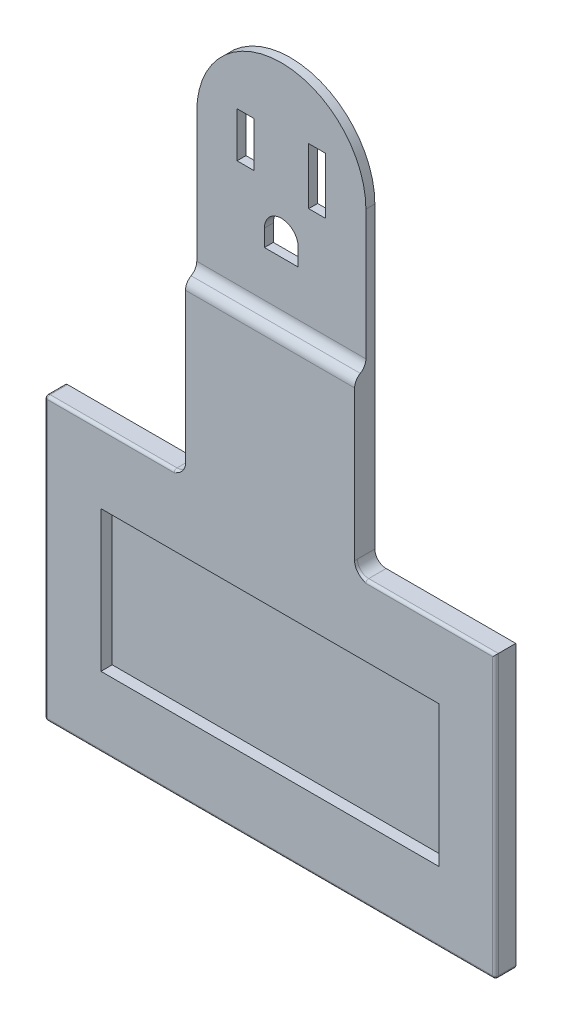
SolidWorks part; units mm, degrees
ref_plane "Front Plane" through (0, 0, 0) normal (0, 0, 1) x (1, 0, 0)
ref_plane "Top Plane" through (0, 0, 0) normal (0, 1, 0) x (1, 0, 0)
ref_plane "Right Plane" through (0, 0, 0) normal (1, 0, 0) x (0, 0, -1)
sketch "Sketch1" plane through (0, 0, 0) normal (0, 0, 1) x (1, 0, 0)
  line L0 (8.022, -0.6939) -> (8.022, -8.6939) construction
  line L1 (19.222, 0.3061) -> (22.222, 0.3061)
  line L2 (19.222, 0.3061) -> (19.222, -9.6939)
  line L3 (19.222, -9.6939) -> (22.222, -9.6939)
  line L4 (22.222, 0.3061) -> (22.222, -9.6939)
  line L5 (9.522, -0.6939) -> (6.522, -0.6939)
  line L6 (9.522, -0.6939) -> (9.522, -8.6939)
  line L7 (9.522, -8.6939) -> (6.522, -8.6939)
  line L8 (6.522, -0.6939) -> (6.522, -8.6939)
  line L9 (20.722, 0.3061) -> (20.722, -9.6939) construction
  line L10 (8.022, -4.6939) -> (20.722, -4.6939) construction
  line L11 (11.372, -16.5939) -> (11.372, -19.5939)
  line L12 (11.372, -19.5939) -> (17.372, -19.5939)
  line L13 (17.372, -19.5939) -> (17.372, -16.5939)
  line L14 (17.372, -16.5939) -> (11.372, -16.5939)
  line L15 (14.372, -4.6939) -> (14.372, -4.0617) construction
  line L16 (29.372, -4.6939) -> (29.372, -59.6939)
  line L17 (29.372, -59.6939) -> (-0.628, -59.6939)
  line L18 (-0.628, -59.6939) -> (-0.628, -4.6939)
  arc A0 (17.372, -16.5939) -> (11.372, -16.5939) centre (14.372, -16.5939) ccw
  arc A1 (29.372, -4.6939) -> (-0.628, -4.6939) centre (14.372, -4.6939) ccw
  dimension "D8" = 3
  dimension "D11" = 30
  dimension "D1" = 10
  dimension "D2" = 3
  dimension "D3" = 8
  dimension "D4" = 3
  dimension "D5" = 12.7
  dimension "D6" = 0
  dimension "D7" = 6
  dimension "D9" = 0
  dimension "D10" = 11.9
  dimension "D12" = 55
extrude "Boss-Extrude1" add sketch "Sketch1" along normal blind 1.5875 contours L16 A1 L18 L17 L1 L4 L3 L2 L8 L5 L6 L7 A0 L13 L12 L11
ref_plane "Plane1" through (14.372, 0, 0) normal (1, 0, 0) x (0, 0, -1)
sketch "Sketch3" plane through (14.372, 0, 0) normal (1, 0, 0) x (0, 0, -1)
  line L0 (0, -59.6939) -> (0, -109.6939)
  line L1 (0, -109.6939) -> (-1.5875, -109.6939)
  line L2 (-1.5875, -109.6939) -> (-1.5875, -59.6939)
  line L3 (-1.5875, -109.6939) -> (-3.5875, -109.6939)
  line L4 (-3.5875, -109.6939) -> (-3.5875, -59.6939)
  line L5 (-3.5875, -59.6939) -> (-1.5875, -59.6939)
  line L6 (-1.5875, -59.6939) -> (0, -59.6939)
  dimension "D1" = 50
  dimension "D2" = 2
extrude "Boss-Extrude2" add sketch "Sketch3" along normal blind 40 and the other way blind 40 contours L5 L4 L3 L2 | L6 L2 L1 L0
sketch "Sketch6" plane through (29.372, 0, 0) normal (1, 0, 0) x (0, 0, -1)
  line L0 (-1.5875, -59.6939) -> (-3.5875, -59.6939)
  line L1 (-3.5875, -59.6939) -> (-3.5875, -29.6939)
  line L2 (-3.5875, -29.6939) -> (-1.5875, -29.6939)
  line L3 (-1.5875, -4.6939) -> (-1.5875, -59.6939) construction
  line L4 (-1.5875, -29.6939) -> (-1.5875, -59.6939)
  line L5 (-1.5875, -59.6939) -> (-1.6981, -59.3827)
  dimension "D1" = 30
extrude "Boss-Extrude3" add sketch "Sketch6" against normal blind 30 contours L0 L1 L2 L4
sketch "Sketch4" plane through (0, 0, 3.5875) normal (0, 0, 1) x (1, 0, 0)
  line L0 (-15.628, -72.1939) -> (44.372, -72.1939)
  line L1 (44.372, -72.1939) -> (44.372, -97.1939)
  line L2 (44.372, -97.1939) -> (-15.628, -97.1939)
  line L3 (-15.628, -97.1939) -> (-15.628, -72.1939)
  line L4 (-25.628, -109.6939) -> (-25.628, -59.6939) construction
  line L5 (-25.628, -59.6939) -> (-0.628, -59.6939) construction
  dimension "D1" = 60
  dimension "D2" = 25
  dimension "D3" = 10
  dimension "D4" = 12.5
extrude "Cut-Extrude1" cut sketch "Sketch4" against normal blind 2
fillet "Fillet3" radius 0.5 11 edges at (-13.128, -59.6939, 3.5875) (54.372, -109.6939, 1.7937) (14.372, -109.6939, 3.5875) (54.372, -84.6939, 3.5875) (-25.628, -59.6939, 1.7937) (-25.628, -109.6939, 1.7937) (-25.628, -84.6939, 3.5875) (41.872, -59.6939, 3.5875)
fillet "Fillet5" radius 2 9 edges at (-0.628, -59.8403, 3.4411) (29.372, -59.8403, 3.4411) (14.372, -29.6939, 1.5875) (29.372, -29.6939, 2.5875) (-0.628, -29.6939, 2.5875)
fillet "Fillet6" radius 2 1 edges at (14.372, -29.6939, 3.5875)
